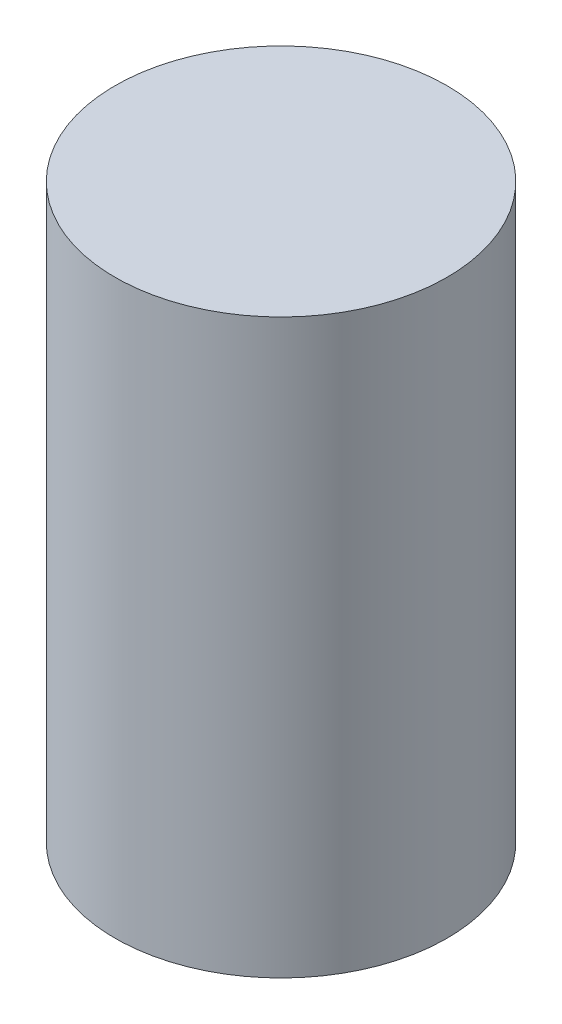
SolidWorks part; units mm, degrees
ref_plane "Front Plane" through (0, 0, 0) normal (0, 0, 1) x (1, 0, 0)
ref_plane "Top Plane" through (0, 0, 0) normal (0, 1, 0) x (1, 0, 0)
ref_plane "Right Plane" through (0, 0, 0) normal (1, 0, 0) x (0, 0, -1)
sketch "Sketch1" plane through (0, 0, 0) normal (0, 1, 0) x (1, 0, 0)
  circle A0 centre (0, 0) radius 3.683
  dimension "D1" = 7.366
extrude "Boss-Extrude1" add sketch "Sketch1" along normal blind 12.7 contours A0
